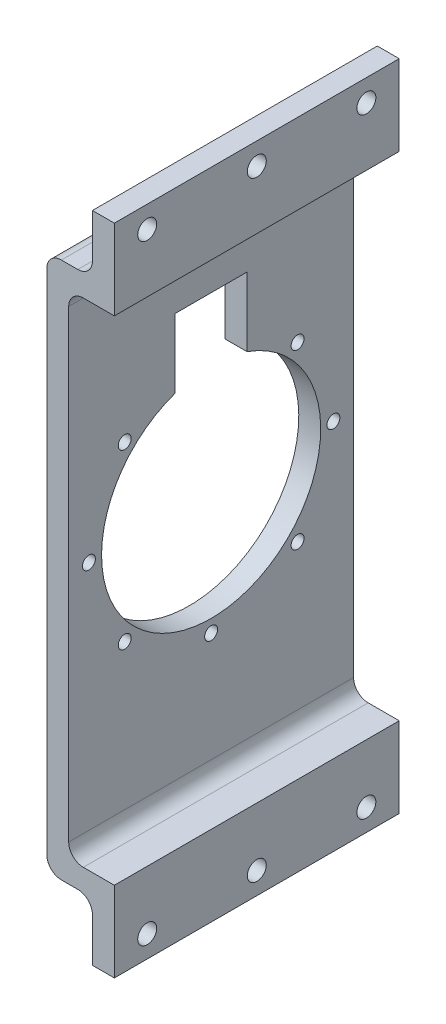
SolidWorks part; units mm, degrees
other "Markup1"
sketch "Sketch9" plane through (-7.62, -27.94, -49.53) normal (-1, 0, 0) x (0, 0, 1)
sketch "Sketch12" plane through (-7.62, -27.94, -49.53) normal (-1, 0, 0) x (0, 0, 1)
sketch "Sketch13" plane through (-7.62, -27.94, -49.53) normal (-1, 0, 0) x (0, 0, 1)
sketch "Sketch15" plane through (-7.62, -27.94, -49.53) normal (-1, 0, 0) x (0, 0, 1)
material "ABS"
ref_plane "Front Plane" through (0, 0, 0) normal (0, 0, 1) x (1, 0, 0)
ref_plane "Top Plane" through (0, 0, 0) normal (0, 1, 0) x (1, 0, 0)
ref_plane "Right Plane" through (0, 0, 0) normal (1, 0, 0) x (0, 0, -1)
sketch "Sketch1" plane through (0, 0, 0) normal (0, 0, 1) x (1, 0, 0)
  line L0 (0, 0) -> (0, 171.45)
  line L1 (0, 0) -> (15.875, 0)
  line L2 (-7.62, -7.62) -> (-7.62, 171.45)
  line L3 (-7.62, -7.62) -> (8.255, -7.62)
  line L5 (15.875, 0) -> (15.875, -7.62)
  line L8 (0, 171.45) -> (15.875, 171.45)
  line L9 (-7.62, 171.45) -> (-7.62, 179.07)
  line L10 (-7.62, 179.07) -> (8.255, 179.07)
  line L11 (15.875, 171.45) -> (15.875, 179.07)
  line L12 (15.875, -7.62) -> (15.875, -27.94)
  line L13 (15.875, -27.94) -> (8.255, -27.94)
  line L14 (8.255, -27.94) -> (8.255, -7.62)
  line L15 (15.875, 179.07) -> (15.875, 199.39)
  line L16 (-7.62, -7.62) -> (15.875, -7.62) construction
  line L17 (15.875, 199.39) -> (8.255, 199.39)
  line L18 (8.255, 199.39) -> (8.255, 179.07)
  dimension "D3" = 20.32
  dimension "D4" = 171.45
  dimension "D2" = 15.875
  dimension "D1" = 7.62
extrude "Boss-Extrude1" add sketch "Sketch1" along normal mid plane 99.06
ref_plane "Actuator Plane" through (0, 85.725, 0) normal (0, 1, 0) x (1, 0, 0)
fillet "Fillet1" radius 5.08 6 edges at (0, 0, 0) (8.255, -7.62, 0) (0, 171.45, 0) (8.255, 179.07, 0) (-7.62, 179.07, 0) (-7.62, -7.62, 0)
sketch "Sketch7" plane through (0, 0, 0) normal (1, 0, 0) x (0, 0, -1)
  line L0 (4.191, 85.725) -> (-4.191, 85.725) construction
  line L3 (-39.2649, 101.989) -> (0, 85.725) construction
  line L4 (0, 85.725) -> (-42.5, 85.725) construction
  circle A0 centre (0, 85.725) radius 42.5 construction
  circle A1 centre (-42.5, 85.725) radius 2.25
  circle A2 centre (-30.052, 115.777) radius 2.25
  circle A3 centre (0, 128.225) radius 2.25
  circle A4 centre (30.052, 115.777) radius 2.25
  circle A5 centre (42.5, 85.725) radius 2.25
  circle A6 centre (30.052, 55.673) radius 2.25
  circle A7 centre (0, 43.225) radius 2.25
  circle A8 centre (-30.052, 55.673) radius 2.25
  circle A9 centre (-39.2649, 101.989) radius 1.75 construction
  circle A10 centre (-16.264, 124.9899) radius 1.75 construction
  circle A11 centre (16.264, 124.9899) radius 1.75 construction
  circle A12 centre (39.2649, 101.989) radius 1.75 construction
  circle A13 centre (39.2649, 69.461) radius 1.75 construction
  circle A14 centre (16.264, 46.4601) radius 1.75 construction
  circle A15 centre (-16.264, 46.4601) radius 1.75 construction
  circle A16 centre (-39.2649, 69.461) radius 1.75 construction
  circle A17 centre (0, 85.725) radius 38.1
  point P28 (0, 85.725)
  point P45 (0, 85.725)
  dimension "D1" = 4.5
  dimension "D2" = 85
  dimension "D5" = 3.5
  dimension "D7" = 76.2
  dimension "D4" = 22.5
  dimension "D3" = 8
  dimension "D6" = 8
extrude "Cut-Extrude1" cut sketch "Sketch7" against normal up to surface (7.62 mm away) up to face at (-7.62, 85.725, 0)
sketch "Sketch8" plane through (8.255, 0, 0) normal (-1, 0, 0) x (0, 0, 1)
  line L0 (-38.1, 191.77) -> (0, 191.77) construction
  line L1 (0, 191.77) -> (38.1, 191.77) construction
  line L2 (0, -12.9223) -> (0, 12.9223) construction
  line L4 (-49.53, 199.39) -> (-49.53, 184.15) construction
  circle A0 centre (-38.1, 191.77) radius 3.302
  circle A1 centre (0, 191.77) radius 3.302
  circle A3 centre (38.1, 191.77) radius 3.302
  point P17 (-49.53, 191.77)
  dimension "D4" = 6.604
  dimension "D2" = 76.2
extrude "Cut-Extrude2" cut sketch "Sketch8" against normal up to surface (7.62 mm away) up to face at (15.875, 185.42, 0)
mirror "Mirror1" about plane through (0, 85.725, 0) normal (0, 1, 0) of "Cut-Extrude2"
sketch "Sketch14" plane through (-7.62, 0, 0) normal (-1, 0, 0) x (0, 0, 1)
  line L0 (12.5, 121.7161) -> (12.5, 145.725)
  line L1 (12.5, 145.725) -> (-12.5, 145.725)
  line L2 (-12.5, 145.725) -> (-12.5, 121.7161)
  circle A0 centre (0, 85.725) radius 38.1 construction
  arc A1 (12.5, 121.7161) -> (-12.5, 121.7161) centre (0, 85.725) ccw
  point P10 (0, 145.725)
  dimension "D1" = 25
  dimension "D2" = 60
extrude "Cut-Extrude3" cut sketch "Sketch14" against normal up to surface (7.62 mm away) up to face at (0, 85.725, 40.25)
equation "\"VerticalHeight\"= 6.75"
equation "\"D4@Sketch1\"=\"VerticalHeight\""
